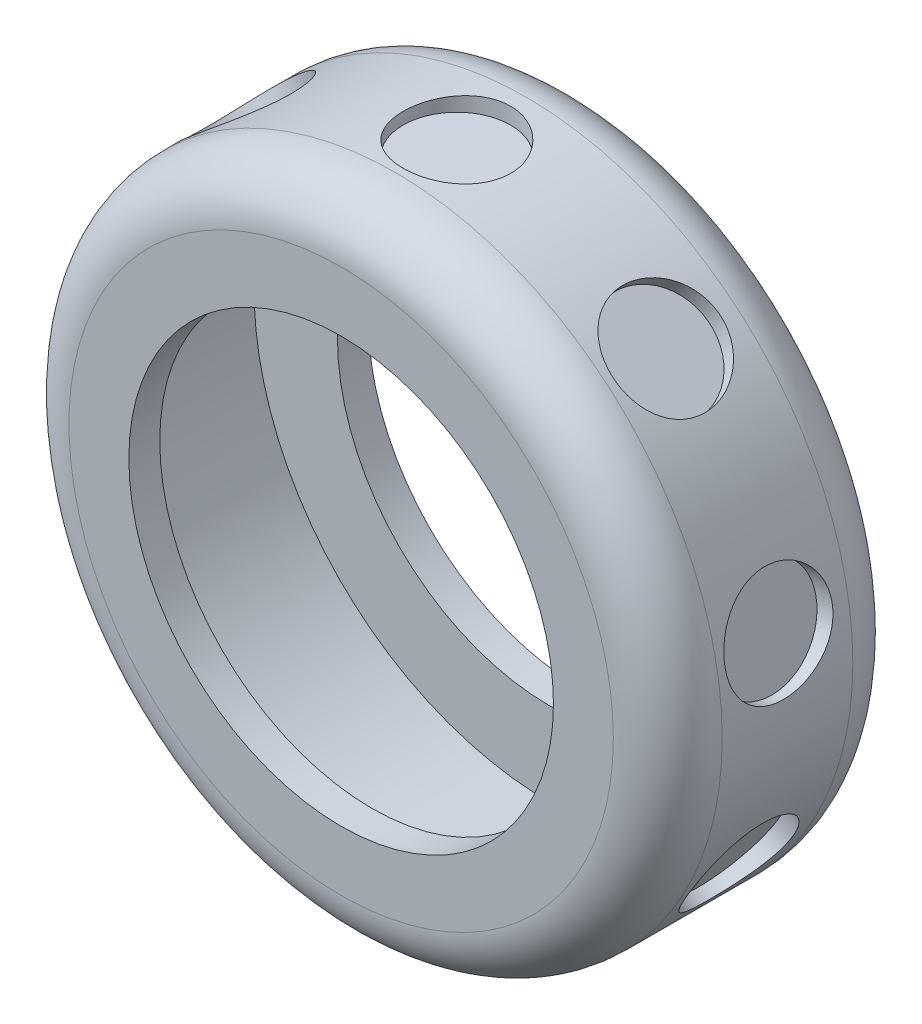
SolidWorks part; units mm, degrees
ref_plane "Front Plane" through (0, 0, 0) normal (0, 0, 1) x (1, 0, 0)
ref_plane "Top Plane" through (0, 0, 0) normal (0, 1, 0) x (1, 0, 0)
ref_plane "Right Plane" through (0, 0, 0) normal (1, 0, 0) x (0, 0, -1)
sketch "Sketch5" plane through (0, 0, 0) normal (0, 0, 1) x (1, 0, 0)
  circle A0 centre (0, 0) radius 30
extrude "Boss-Extrude2" add sketch "Sketch5" along normal blind 22
sketch "Sketch6" plane through (0, 0, 0) normal (0, 0, 1) x (1, 0, 0)
  circle A0 centre (0, 0) radius 19.5
  dimension "D1" = 39
extrude "Cut-Extrude3" cut sketch "Sketch6" along direction (0, 0, 1) on the side of the normal blind 22 contours A0
shell "Shell4" thickness 2.84 removed face at (19.5, 0, 22)
fillet "Fillet2" radius 5 2 edges at (30, 0, 0) (30, 0, 22)
ref_plane "Plane1" through (0, 28.5, 0) normal (0, 1, 0) x (1, 0, 0)
sketch "Sketch7" plane through (0, 28.5, 0) normal (0, 1, 0) x (1, 0, 0)
  line L0 (0, -12.1) -> (0, 12.1) construction
  circle A0 centre (0, -11.3725) radius 4.9386
extrude "Cut-Extrude4" cut sketch "Sketch7" along normal blind 22 contours A0
ref_axis "Axis1" through (0, 0, 23.1) along (0, 0, -1)
pattern_circular "CirPattern1" count 9 every 40 about axis through (0, 0, 23.1) along (0, 0, -1) of "Cut-Extrude4"
